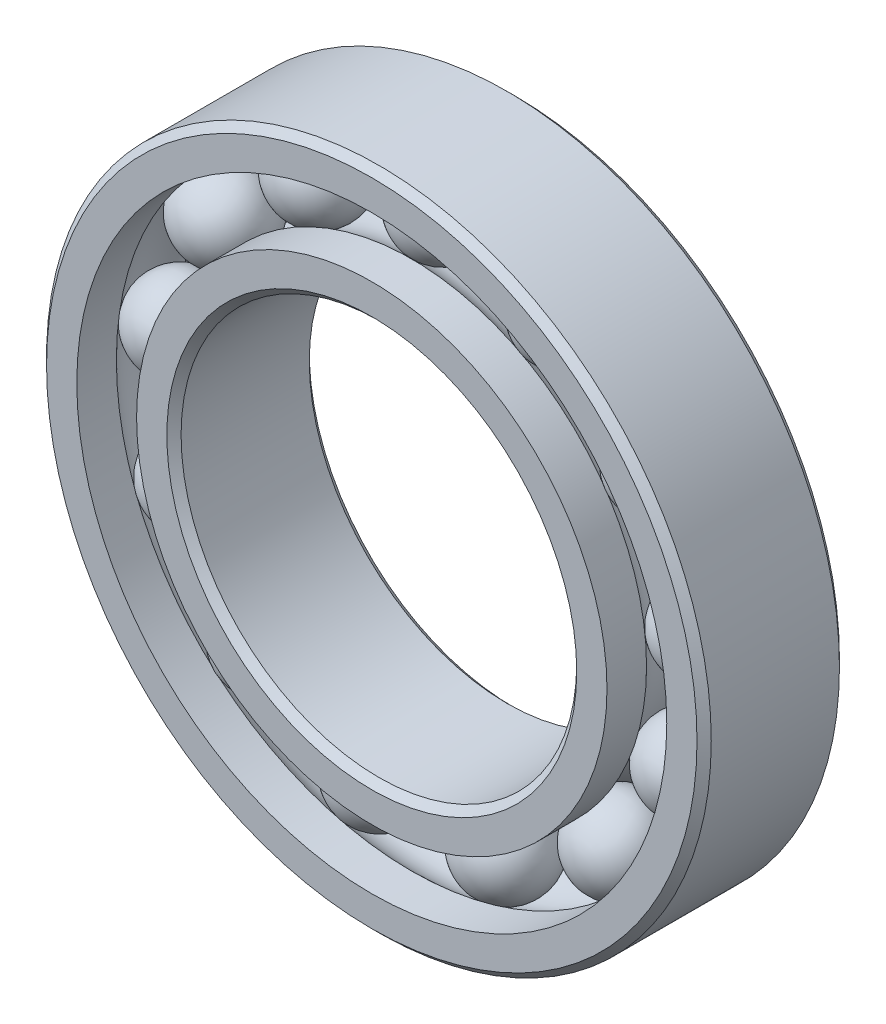
SolidWorks part; units mm, degrees
material "Alloy Steel"
ref_plane "Front Plane" through (0, 0, 0) normal (0, 0, 1) x (1, 0, 0)
ref_plane "Top Plane" through (0, 0, 0) normal (0, 1, 0) x (1, 0, 0)
ref_plane "Right Plane" through (0, 0, 0) normal (1, 0, 0) x (0, 0, -1)
sketch "Sketch1" plane through (0, 0, 0) normal (0, 0, 1) x (1, 0, 0)
  circle A0 centre (0, 0) radius 21
  circle A1 centre (0, 0) radius 12.5
  dimension "OD" = 42
  dimension "ID" = 25
  dimension "For Shaft Diameter" = 25
  dimension "For Housing ID" = 42
sketch "Sketch5" plane through (0, 0, 0) normal (1, 0, 0) x (0, 0, -1)
  line L0 (-4.5, 0) -> (4.5, 0) construction
  line L1 (0, 21) -> (0, -21) construction
  line L2 (4.05, 21) -> (-4.05, 21)
  line L3 (-4.05, 21) -> (-4.5, 20.55)
  line L4 (-4.5, 20.55) -> (-4.5, 18.6389)
  line L5 (-4.5, 18.6389) -> (-2, 18.6389)
  line L6 (4.5, 18.6389) -> (2, 18.6389)
  line L7 (4.5, 20.55) -> (4.5, 18.6389)
  line L8 (4.05, 21) -> (4.5, 20.55)
  line L9 (0, 21) -> (0, 16.75) construction
  line L10 (0, 16.75) -> (0, 12.5) construction
  line L11 (-2.751, 16.75) -> (-4.5, 16.75) construction
  line L12 (3.435, 14.8865) -> (3.816, 14.8865) construction
  line L13 (-3.435, 14.8865) -> (-3.816, 14.8865) construction
  line L14 (-3.435, 14.8865) -> (-3.435, 18.6135) construction
  line L15 (-3.435, 18.6135) -> (-3.816, 18.6135) construction
  line L16 (-3.816, 14.8865) -> (-3.816, 18.6135) construction
  line L17 (-3.435, 14.8865) -> (-3.816, 18.6135) construction
  line L18 (-3.435, 18.6135) -> (-3.816, 14.8865) construction
  line L19 (3.816, 14.8865) -> (3.816, 18.6135) construction
  line L20 (3.435, 18.6135) -> (3.816, 18.6135) construction
  line L21 (3.435, 14.8865) -> (3.435, 18.6135) construction
  line L22 (0, 21) -> (0, -21) construction
  arc A0 (-2, 18.6389) -> (2, 18.6389) centre (0, 16.75) cw
  circle A1 centre (0, 16.75) radius 2.751 construction
  point P14 (0, 12.5)
  point P15 (-3.6255, 16.75)
  dimension "Width" = 9
  dimension "D1" = 45
  dimension "D2" = 0.45
  dimension "D3" = 4
  dimension "D4" = 1.8889
  dimension "D5" = 0.381
  dimension "D6" = 0.0254
  dimension "D7" = 9
revolve "Revolve1" add sketch "Sketch5" angle 360 about L0
sketch "Sketch3" plane through (0, 0, 0) normal (1, 0, 0) x (0, 0, -1)
  line L0 (-4.5, 14.8611) -> (-2, 14.8611)
  line L1 (0, 21) -> (0, -21) construction
  line L2 (-4.5, 20.55) -> (-4.5, 18.6389) construction
  line L3 (-4.5, 14.8611) -> (-4.5, 12.95)
  line L4 (-4.05, 21) -> (-4.5, 20.55) construction
  line L5 (-4.5, 12.95) -> (-4.05, 12.5)
  line L6 (-4.05, 12.5) -> (4.05, 12.5)
  line L7 (4.05, 21) -> (4.05, -21) construction
  line L8 (4.05, 12.5) -> (4.5, 12.95)
  line L9 (4.5, -20.55) -> (4.5, 20.55) construction
  line L10 (4.5, 12.95) -> (4.5, 14.8611)
  line L11 (4.5, 14.8611) -> (2, 14.8611)
  line L13 (4.05, 21) -> (4.5, 20.55) construction
  arc A0 (2, 18.6389) -> (-2, 18.6389) centre (0, 16.75) ccw construction
  arc A1 (2, 14.8611) -> (-2, 14.8611) centre (0, 16.75) cw
revolve "Revolve3" add sketch "Sketch3" angle 360 about L0
sketch "Sketch4" plane through (0, 0, 0) normal (1, 0, 0) x (0, 0, -1)
  line L0 (-2.751, 16.75) -> (2.751, 16.75)
  arc A2 (-2.751, 16.75) -> (2.751, 16.75) centre (0, 16.75) cw
  arc A3 (2, 18.6389) -> (-2, 18.6389) centre (0, 16.75) ccw construction
revolve "Revolve4" add sketch "Sketch4" angle 360 about L0
pattern_circular "CirPattern1" count 13 every 27.692 of bodies 104
ref_axis "Center Axis 1" through (0, 0, -4.05) along (0, 0, 1)
equation "\"D2@Sketch5\" = \"Width@Sketch5\" * .05"
equation "\"D3@Sketch5\" = \"Width@Sketch5\" / 2.25"
equation "\"D4@Sketch5\"=((\"OD@Sketch1\"-\"ID@Sketch1\")/2)/4.5"
equation "\"D2@CirPattern1\" = 360/\"Balls@CirPattern1\""
